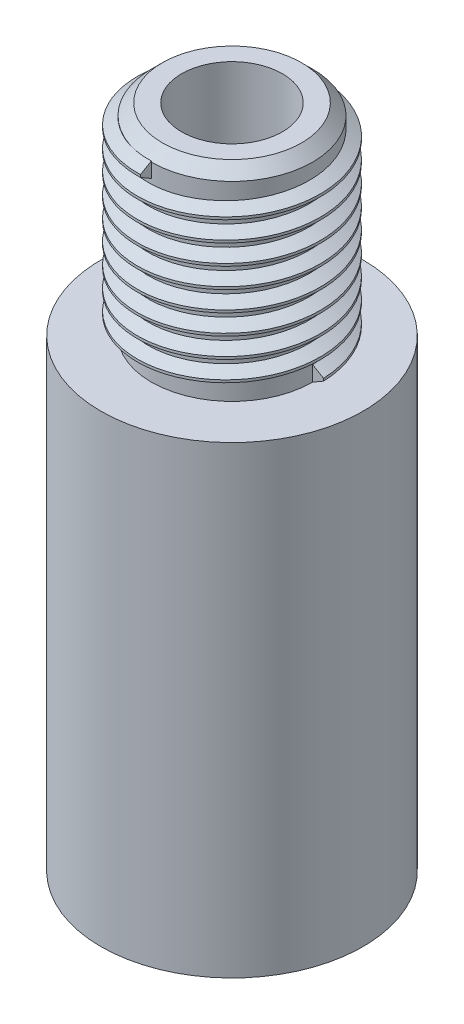
SolidWorks part; units mm, degrees
material "Brass"
ref_plane "Front Plane" through (0, 0, 0) normal (0, 0, 1) x (1, 0, 0)
ref_plane "Top Plane" through (0, 0, 0) normal (0, 1, 0) x (1, 0, 0)
ref_plane "Right Plane" through (0, 0, 0) normal (1, 0, 0) x (0, 0, -1)
sketch "Sketch1" plane through (0, 0, 0) normal (0, 1, 0) x (1, 0, 0)
  circle A0 centre (0, 0) radius 6.5
extrude "Boss-Extrude1" add sketch "Sketch1" along normal blind 23
sketch "Sketch2" plane through (0, 23, 0) normal (0, 1, 0) x (1, 0, 0)
  circle A0 centre (0, 0) radius 4
extrude "Boss-Extrude2" add sketch "Sketch2" along normal blind 10
sketch "Sketch3" plane through (0, 0, 0) normal (0, -1, 0) x (1, 0, 0)
  circle A0 centre (0, 0) radius 2.5
extrude "Cut-Extrude1" cut sketch "Sketch3" against normal through all both and the other way through all
sketch "Sketch4" plane through (0, 0, 0) normal (0, -1, 0) x (1, 0, 0)
  circle A0 centre (0, 0) radius 4.5
extrude "Cut-Extrude2" cut sketch "Sketch4" against normal blind 18 and the other way through all
chamfer "Chamfer1" distance 0.55 angle 45 1 edges at (0, 33, 4)
thread "Thread1" pitch 1 method extrude profile "Thread Profile2" start angle 0, offset 0, length 8.75, pitch 1, diameter 8
ref_plane "Plane2" through (4, 23, 0) normal (0, 0, 1) x (1, 0, 0)
sketch "Thread Profile2" plane through (4, 23, 0) normal (0, 0, 1) x (1, 0, 0)
  line L0 (0, 0) -> (0, 1) construction
  line L1 (0, 0) -> (0.5413, 0.3125)
  line L2 (0.5413, 0.3125) -> (0.5413, 0.4375)
  line L3 (0.5413, 0.4375) -> (0, 0.75)
  line L4 (0.5413, 0.375) -> (0, 0.375) construction
  line L11 (0, 0) -> (0, 0.75)
  point P2 (0, 0)
  dimension "Pitch" = 1
  dimension "Profile_Angle" = 60
  dimension "Profile_Land" = 0.125
  dimension "Profile_Height" = 0.5413
